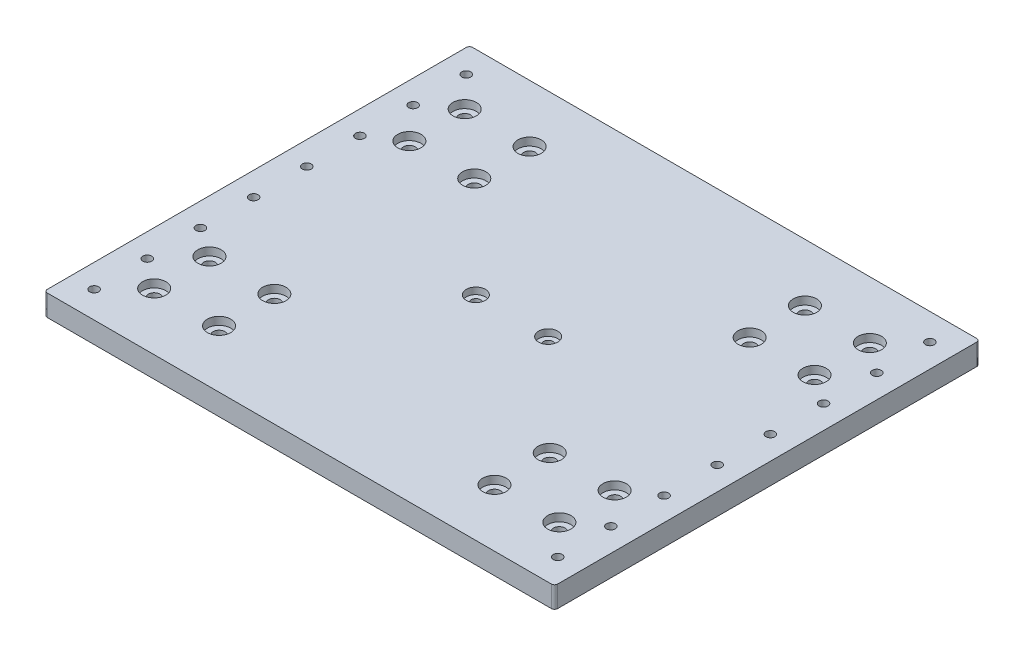
SolidWorks part; units mm, degrees
ref_plane "Front Plane" through (0, 0, 0) normal (0, 0, 1) x (1, 0, 0)
ref_plane "Top Plane" through (0, 0, 0) normal (0, 1, 0) x (1, 0, 0)
ref_plane "Right Plane" through (0, 0, 0) normal (1, 0, 0) x (0, 0, -1)
sketch "Sketch1" plane through (0, 0, 0) normal (0, 1, 0) x (1, 0, 0)
  line L1 (-120, -100) -> (120, -100)
  line L2 (-120, -100) -> (-120, 100)
  line L3 (-120, 100) -> (120, 100)
  line L4 (120, -100) -> (120, 100)
  line L5 (-120, -100) -> (120, 100) construction
  line L6 (-120, 100) -> (120, -100) construction
  point P0 (0, 0)
  dimension "D1" = 240
  dimension "D2" = 200
extrude "Boss-Extrude1" add sketch "Sketch1" along normal mid plane 10
hole_wizard "CBORE for M5 Pan Head Machine Screw1" positions "Sketch11" profile "Sketch10" counterbore size "M5" standard "ANSI Metric" end condition through all
sketch "Sketch11" plane through (66.9231, 5, -81.9693) normal (0, -1, 0) x (-1, 0, 0)
  line L0 (146.9231, -1018.8886) -> (146.9231, 48981.1114) construction
  line L1 (-912.3245, -141.9693) -> (49087.6755, -141.9693) construction
  line L2 (186.9231, 18.0307) -> (186.9231, -181.9693) construction
  line L3 (186.9231, -181.9693) -> (-53.0769, -181.9693) construction
  line L5 (162.1731, -128.9693) -> (131.6731, -128.9693) construction
  line L6 (162.1731, -128.9693) -> (162.1731, -154.9693) construction
  line L7 (162.1731, -154.9693) -> (131.6731, -154.9693) construction
  line L8 (131.6731, -128.9693) -> (131.6731, -154.9693) construction
  line L9 (162.1731, -128.9693) -> (131.6731, -154.9693) construction
  line L10 (162.1731, -154.9693) -> (131.6731, -128.9693) construction
  point P0 (162.1731, -154.9693)
  point P2 (131.6731, -154.9693)
  point P4 (131.6731, -128.9693)
  point P6 (162.1731, -128.9693)
  dimension "D1" = 40
  dimension "D2" = 40
  dimension "D3" = 15.25
  dimension "D4" = 26
  dimension "D5" = 13
  dimension "D6" = 30.5
sketch "Sketch10" plane through (-95.25, 5, 73) normal (1, 0, 0) x (0, 0, 1)
  line L0 (0, 0) -> (0, 10)
  line L1 (0, 10) -> (2.75, 10)
  line L3 (2.75, 10) -> (2.75, 3.7)
  line L4 (2.75, 3.7) -> (5.5, 3.7)
  line L5 (5.5, 3.7) -> (5.5, 0)
  line L7 (5.5, 0) -> (0, 0)
  line L11 (0, -6.35) -> (0, 107.95) construction
  dimension "Thru Hole Dia." = 5.5
  dimension "Thru Hole Depth" = 10
  dimension "C'Bore Dia." = 11
  dimension "C'Bore Depth" = 3.7
mirror "Mirror1" about plane through (0, 0, 0) normal (1, 0, 0) of "CBORE for M5 Pan Head Machine Screw1"
mirror "Mirror2" about plane through (0, 0, 0) normal (0, 0, 1) of "Mirror1"
hole_wizard "CBORE for M4 Pan Head Machine Screw1" positions "Sketch9" profile "Sketch8" counterbore size "M4" standard "ANSI Metric" end condition through all
sketch "Sketch9" plane through (-30.3385, 5, -23.5385) normal (0, -1, 0) x (-1, 0, 0)
  line L0 (-1000, -23.5385) -> (49000, -23.5385) construction
  point P0 (-13.3385, -23.5385)
  point P2 (-47.3385, -23.5385)
  dimension "D1" = 17
  dimension "D2" = 17
sketch "Sketch8" plane through (-17, 5, 0) normal (1, 0, 0) x (0, 0, 1)
  line L0 (0, 0) -> (0, 10)
  line L1 (0, 10) -> (2.25, 10)
  line L3 (2.25, 10) -> (2.25, 3.1)
  line L4 (2.25, 3.1) -> (4.5, 3.1)
  line L5 (4.5, 3.1) -> (4.5, 0)
  line L7 (4.5, 0) -> (0, 0)
  line L11 (0, -6.35) -> (0, 107.95) construction
  dimension "Thru Hole Dia." = 4.5
  dimension "Thru Hole Depth" = 10
  dimension "C'Bore Dia." = 9
  dimension "C'Bore Depth" = 3.1
hole_wizard "M5x0.8 Tapped Hole1" positions "Sketch7" profile "Sketch5" tap size "M5x0.8" standard "ANSI Metric" end condition through all
sketch "Sketch7" plane through (0, 5, 0) normal (0, 1, 0) x (1, 0, 0)
  line L0 (120, 100) -> (-120, 100) construction
  line L1 (-120, 100) -> (-120, -100) construction
  line L2 (120, -100) -> (120, 100) construction
  point P0 (-109, 87.5)
  point P2 (109, 87.5)
  dimension "D1" = 12.5
  dimension "D2" = 11
  dimension "D3" = 11
  dimension "D4" = 12.5
sketch "Sketch5" plane through (-109, 5, -87.5) normal (1, 0, 0) x (0, 0, 1)
  line L0 (0, 0) -> (0, 10)
  line L1 (0, 10) -> (2.1, 10)
  line L2 (2.1, 10) -> (2.1, 0)
  line L5 (2.1, 0) -> (0, 0)
  line L11 (0, -6.35) -> (0, 107.95) construction
  dimension "Thru Tap Drill Dia." = 4.2
  dimension "Thru Tap Drill Depth" = 10
cosmetic thread "Hole Thread1" parameters "D2"=5
cosmetic thread "Hole Thread2" parameters "D2"=5
fillet "Fillet1" radius 1.5 4 edges at (-120, 0, -100) (120, 0, -100) (-120, 0, 100) (120, 0, 100)
pattern_linear "LPattern2" count 8 spacing 25 along (0, 0, 1) of "M5x0.8 Tapped Hole1"
